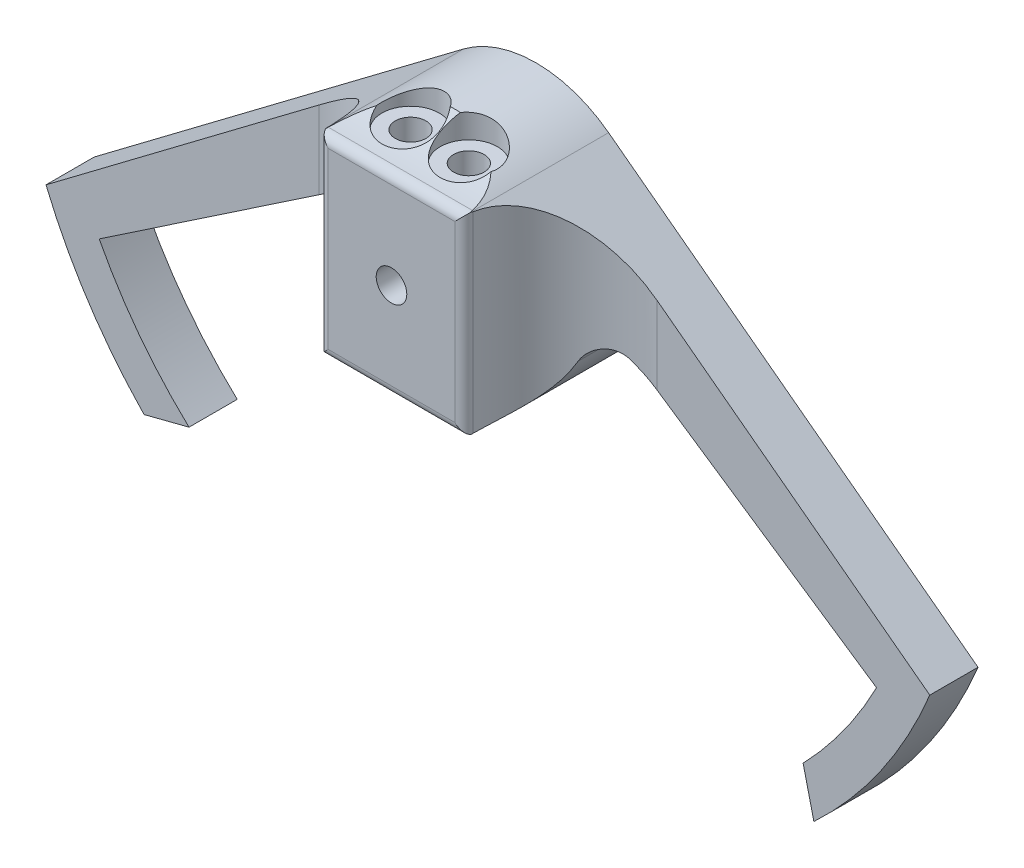
SolidWorks part; units mm, degrees
ref_plane "Front Plane" through (0, 0, 0) normal (0, 0, 1) x (1, 0, 0)
ref_plane "Top Plane" through (0, 0, 0) normal (0, 1, 0) x (1, 0, 0)
ref_plane "Right Plane" through (0, 0, 0) normal (1, 0, 0) x (0, 0, -1)
sketch "Sketch1" plane through (0, 0, 0) normal (0, 0, 1) x (1, 0, 0)
  line L0 (-15.0425, 19.968) -> (-91.677, -37.7631)
  line L1 (-80.6339, -41.9641) -> (-24.6431, -4.2093)
  line L2 (-90.9981, -49.7717) -> (-1.4919, 17.6561) construction
  line L3 (15.0425, 19.968) -> (91.677, -37.7631)
  line L4 (30.4403, -4.1516) -> (104.5688, -59.995) construction
  line L5 (80.6339, -41.9641) -> (24.6431, -4.2093)
  line L6 (67.6304, -72.5041) -> (65.3969, -63.1352)
  line L7 (-62.0031, -66.4713) -> (-71.3323, -68.8653)
  line L8 (-62.0031, -66.4713) -> (0, 0) construction
  line L9 (0, 0) -> (-71.3323, -68.8653) construction
  line L10 (67.6304, -72.5041) -> (0, 0) construction
  line L11 (65.3969, -63.1352) -> (0, 0) construction
  line L12 (0, 0) -> (0, 118.1483) construction
  line L13 (-69.2561, 70.9529) -> (69.2561, 70.9529) construction
  circle A0 centre (0, 0) radius 25
  circle A1 centre (0, 0) radius 99.15 construction
  circle A2 centre (0, 0) radius 90.9 construction
  arc A3 (-80.6339, -41.9641) -> (-62.0031, -66.4713) centre (0, 0) ccw
  arc A4 (-91.677, -37.7631) -> (-71.3323, -68.8653) centre (0, 0) ccw
  arc A5 (65.3969, -63.1352) -> (80.6339, -41.9641) centre (0, 0) ccw
  arc A6 (67.6304, -72.5041) -> (91.677, -37.7631) centre (0, 0) ccw
  dimension "D1" = 50
  dimension "D2" = 181.8
  dimension "D3" = 198.3
  dimension "D4" = 7
  dimension "D5" = 3
  dimension "D6" = 3
  dimension "D7" = 127.4
  dimension "D8" = 3
  dimension "D9" = 3
  dimension "D10" = 10
  dimension "D12" = 10
  dimension "D13" = 7
extrude "Boss-Extrude1" add sketch "Sketch1" along normal blind 10 contours A0 | L0 A4 L7 A3 L1 A0 | L6 A6 L3 A0 L5 A5
sketch "Sketch2" plane through (0, 0, 10) normal (0, 0, 1) x (1, 0, 0)
  line L0 (-15.0425, 19.968) -> (15.0425, 19.968)
  line L1 (15.0425, 19.968) -> (15.0425, -19.968)
  line L2 (15.0425, -19.968) -> (-15.0425, -19.968)
  line L3 (-15.0425, -19.968) -> (-15.0425, 19.968)
  arc A0 (15.0425, 19.968) -> (-15.0425, 19.968) centre (0, 0) ccw construction
  arc A1 (-24.6431, -4.2093) -> (24.6431, -4.2093) centre (0, 0) ccw construction
extrude "Boss-Extrude2" add sketch "Sketch2" along normal blind 20
fillet "Fillet1" radius 20 4 edges at (-21.35, -13.0069, 10) (21.35, -13.0069, 10) (-15.0425, 0, 10) (15.0425, 0, 10)
sketch "Sketch3" plane through (0, 19.968, 0) normal (0, 1, 0) x (1, 0, 0)
  line L0 (-15.0425, -10) -> (-15.0425, -30) construction
  line L1 (15.0425, -10) -> (15.0425, -30) construction
  circle A0 centre (-6.0425, -20) radius 3.175
  circle A1 centre (6.0425, -20) radius 3.175
  point P6 (-15.0425, -20)
  dimension "D3" = 6.35
  dimension "D4" = 6.35
  dimension "D1" = 9
  dimension "D2" = 9
  dimension "D5" = 12.0851
extrude "Cut-Extrude1" cut sketch "Sketch3" against normal through all both and the other way through all
fillet "Fillet3" radius 20 1 edges at (0, -19.968, 10)
sketch "Sketch4" plane through (0, 19.968, 0) normal (0, 1, 0) x (1, 0, 0)
  circle A0 centre (6.0425, -20) radius 5.9531
  circle A1 centre (-6.0425, -20) radius 5.9531
  dimension "D1" = 11.9062
  dimension "D2" = 11.9062
fillet "Fillet5" radius 20 1 edges at (0, 19.968, 10)
extrude "Cut-Extrude2" cut sketch "Sketch4" along normal blind 31
fillet "Fillet7" radius 5 2 edges at (24.6431, -4.2093, 6.4582) (-24.6431, -4.2093, 6.4582)
fillet "Fillet9" radius 2 4 edges at (0, -19.968, 30) (15.0425, 0, 30) (0, 19.968, 30) (-15.0425, 0, 30)
sketch "Sketch5" plane through (0, 0, 30) normal (0, 0, 1) x (1, 0, 0)
  circle A0 centre (0, 0) radius 3.175
  dimension "D1" = 6.35
extrude "Cut-Extrude3" cut sketch "Sketch5" against normal through all
